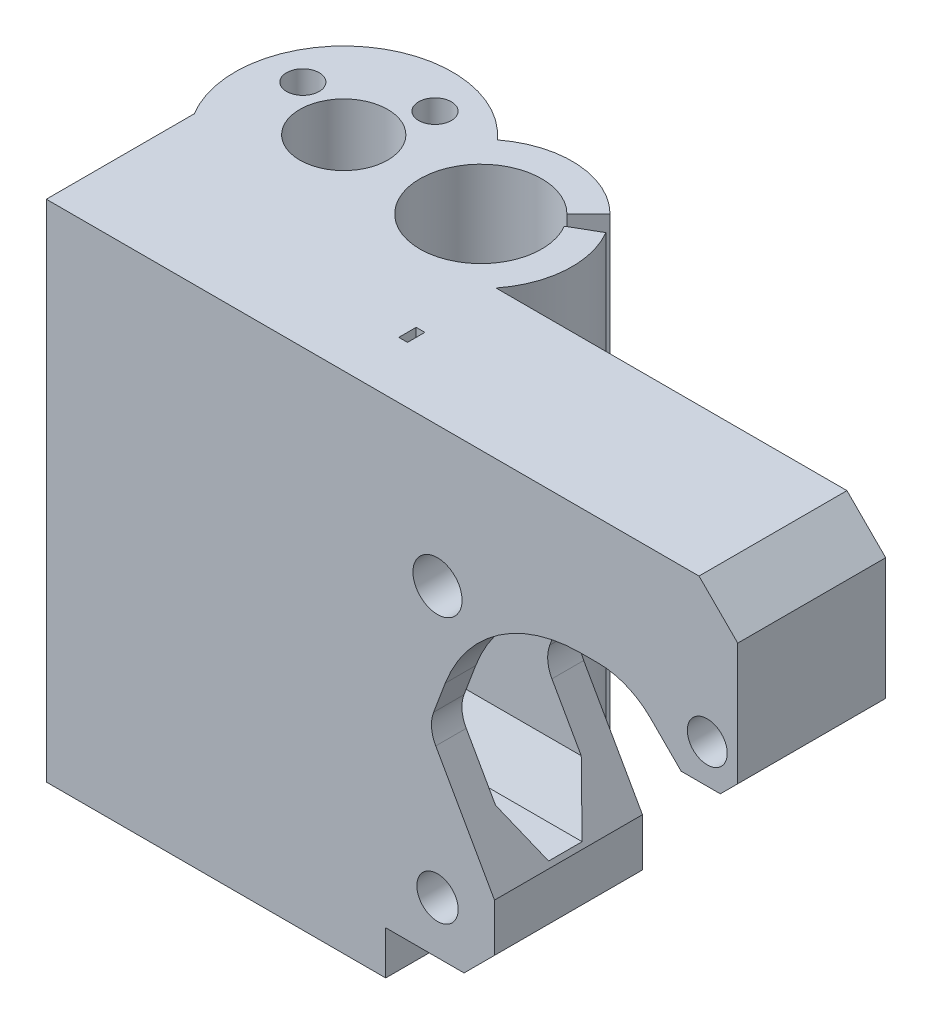
SolidWorks part; units mm, degrees
ref_plane "Front Plane" through (0, 0, 0) normal (0, 0, 1) x (1, 0, 0)
ref_plane "Top Plane" through (0, 0, 0) normal (0, 1, 0) x (1, 0, 0)
ref_plane "Right Plane" through (0, 0, 0) normal (1, 0, 0) x (0, 0, -1)
sketch "Sketch1" plane through (0, 0, 0) normal (0, 0, 1) x (1, 0, 0)
  line L0 (39, -53) -> (48, -53)
  line L1 (0, 0) -> (39, 0)
  line L2 (0, 0) -> (0, -58)
  line L3 (0, -58) -> (39, -58)
  line L4 (39, -53) -> (39, -58)
  line L5 (39, 0) -> (75, 0)
  line L6 (75, 0) -> (79.45, -4.45)
  line L7 (79.45, -4.45) -> (79.45, -18.45)
  line L8 (79.45, -18.45) -> (77.45, -20.45)
  line L9 (77.45, -20.45) -> (72.95, -20.45)
  line L10 (72.95, -20.45) -> (69.45, -16.95)
  line L12 (45.8405, -25.2376) -> (44.5009, -28.8048)
  line L13 (44.75, -32.0294) -> (51.5, -44)
  line L14 (51.5, -44) -> (51.5, -49.5)
  line L15 (61.4145, -14.45) -> (63.4145, -14.45)
  line L16 (51.5, -49.5) -> (48, -53)
  arc A5 (63.4145, -14.45) -> (69.45, -16.95) centre (63.4145, -22.9855) cw
  arc A6 (61.4145, -14.45) -> (45.8405, -25.2376) centre (61.4145, -31.0859) ccw
  arc A7 (44.5009, -28.8048) -> (44.75, -32.0294) centre (48.083, -30.15) ccw
  dimension "D1" = 58
  dimension "D2" = 39
  dimension "D3" = 75
  dimension "D4" = 4.45
  dimension "D5" = 135
  dimension "D6" = 14
  dimension "D7" = 2
  dimension "D8" = 3.5
  dimension "D9" = 6
  dimension "D10" = 5
  dimension "D11" = 4.5
  dimension "D12" = 130
  dimension "D13" = 3.5
  dimension "D14" = 5.5
  dimension "D15" = 6.75
  dimension "D16" = 9
  dimension "D17" = 13.85
  dimension "D18" = 3.417
  dimension "D19" = 2
extrude "Boss-Extrude1" add sketch "Sketch1" along normal blind 17
sketch "Sketch2" plane through (0, 0, 0) normal (0, 1, 0) x (1, 0, 0)
  line L0 (0, -17) -> (0, 6.5) construction
  line L1 (0, 6.5) -> (26.427, 6.5) construction
  circle A0 centre (26.427, 6.5) radius 10.5
  dimension "D2" = 21
  dimension "D1" = 23.5
  dimension "D3" = 26.427
extrude "Boss-Extrude2" add sketch "Sketch2" against normal up to surface (58 mm away) up to face at (19.5, -58, 8.5)
sketch "Sketch3" plane through (0, 0, 0) normal (0, 1, 0) x (1, 0, 0)
  line L0 (0, -17) -> (0, 20.4292) construction
  line L1 (10.6771, 6.5) -> (0, 6.5) construction
  line L2 (75, -17) -> (0, -17) construction
  circle A0 centre (10.6771, 6.5) radius 12.5
  dimension "D3" = 25
  dimension "D2" = 23.5
extrude "Boss-Extrude3" add sketch "Sketch3" against normal blind 13.5
sketch "Sketch4" plane through (0, 0, 0) normal (0, 1, 0) x (1, 0, 0)
  circle A0 centre (26.427, 6.5) radius 7
  circle A1 centre (10.6771, 6.5) radius 5.05
  dimension "D1" = 10.1
  dimension "D2" = 14
extrude "Cut-Extrude1" cut sketch "Sketch4" against normal through all
sketch "Sketch5" plane through (0, 0, 0) normal (-1, 0, 0) x (0, 0, 1)
  line L0 (10.5, -43.5) -> (6.65, -43.5)
  line L1 (6.65, -43.5) -> (3.65, -38)
  line L2 (3.65, -38) -> (3.65, -19)
  line L3 (3.65, -19) -> (6.65, -16)
  line L4 (6.65, -16) -> (10.5, -16)
  line L5 (10.5, -16) -> (13.5, -19)
  line L6 (13.5, -19) -> (13.5, -38)
  line L7 (13.5, -38) -> (10.5, -43.5)
  line L8 (17, 0) -> (0, 0) construction
  line L9 (17, 0) -> (17, -58) construction
  circle A0 centre (8.5, -6) radius 4.05
  circle A1 centre (8.5, -51) radius 4.05
  dimension "D8" = 8.1
  dimension "D9" = 8.1
  dimension "D1" = 19
  dimension "D2" = 3
  dimension "D3" = 3.85
  dimension "D4" = 16
  dimension "D5" = 6
  dimension "D6" = 51
  dimension "D7" = 5.5
  dimension "D10" = 3
  dimension "D11" = 3
  dimension "D12" = 19
  dimension "D13" = 3.85
  dimension "D14" = 3
  dimension "D15" = 3
  dimension "D16" = 3.5
  dimension "D17" = 8.5
  dimension "D18" = 8.5
extrude "Cut-Extrude2" cut sketch "Sketch5" against normal blind 35
sketch "Sketch6" plane through (0, 0, 0) normal (0, 0, -1) x (-1, 0, 0)
  line L0 (-75.9503, -16.0252) -> (-44.9503, -16.0252) construction
  line L1 (-44.9503, -16.0252) -> (-44.9503, -47.0252) construction
  line L2 (-44.9503, -47.0252) -> (-75.9503, -47.0252) construction
  line L3 (-75.9503, -47.0252) -> (-75.9503, -16.0252) construction
  line L4 (-75.9503, -31.5252) -> (-44.9503, -31.5252) construction
  line L5 (-60.4503, -16.0252) -> (-60.4503, -47.0252) construction
  circle A0 centre (-75.9503, -16.0252) radius 2.2933
  circle A1 centre (-44.9503, -16.0252) radius 2.8225
  circle A2 centre (-44.9503, -47.0252) radius 2.3733
  circle A3 centre (-60.4503, -31.5252) radius 11 construction
  point P14 (-60.4503, -31.5252)
  dimension "D3" = 22
  dimension "D1" = 31
  dimension "D2" = 31
extrude "Cut-Extrude3" cut sketch "Sketch6" against normal through all
sketch "Sketch8" plane through (35, 0, 0) normal (-1, 0, 0) x (0, 0, 1)
  line L8 (10.5, -43.5) -> (13.5, -38)
  line L9 (13.5, -38) -> (13.5, -19)
  line L10 (13.5, -19) -> (10.5, -16)
  line L11 (10.5, -16) -> (6.65, -16)
  line L12 (6.65, -16) -> (3.65, -19)
  line L13 (3.65, -19) -> (3.65, -38)
  line L14 (3.65, -38) -> (6.65, -43.5)
  line L15 (6.65, -43.5) -> (10.5, -43.5)
  line L16 (10.5, -43.5) -> (13.5, -38)
  line L17 (13.5, -38) -> (13.5, -19)
  line L18 (13.5, -19) -> (10.5, -16)
  line L19 (10.5, -16) -> (6.65, -16)
  line L20 (6.65, -16) -> (3.65, -19)
  line L21 (3.65, -19) -> (3.65, -38)
  line L22 (3.65, -38) -> (6.65, -43.5)
  line L23 (6.65, -43.5) -> (10.5, -43.5)
  dimension "D1" = 0
extrude "Cut-Extrude4" cut sketch "Sketch8" against normal blind 20
sketch "Sketch9" plane through (0, 0, 0) normal (0, 1, 0) x (1, 0, 0)
  line L0 (32.4461, 10.0735) -> (35.4774, 11.8236)
  line L1 (31.3767, 11.4497) -> (33.8516, 13.9246)
  line L2 (26.427, 6.5) -> (36.927, 6.5) construction
  line L3 (32.4461, 10.0735) -> (26.427, 6.5) construction
  line L4 (26.427, 6.5) -> (31.3767, 11.4497) construction
  arc A0 (32.4461, 10.0735) -> (31.3767, 11.4497) centre (26.427, 6.5) ccw
  arc A1 (35.4774, 11.8236) -> (33.8516, 13.9246) centre (26.427, 6.5) ccw
  arc A2 (34.6732, 0) -> (20.0124, 14.8128) centre (26.427, 6.5) ccw construction
  circle A3 centre (26.427, 6.5) radius 7 construction
  dimension "D1" = 15
  dimension "D2" = 30
extrude "Cut-Extrude5" cut sketch "Sketch9" against normal through all
sketch "Sketch10" plane through (0, 0, 0) normal (0, 1, 0) x (1, 0, 0)
  line L0 (13.5702, 14.0925) -> (10.6771, 6.5) construction
  line L1 (10.6771, 6.5) -> (3.0846, 9.3931) construction
  circle A0 centre (13.5702, 14.0925) radius 1.875
  circle A1 centre (3.0846, 9.3931) radius 1.875
  dimension "D3" = 3.75
  dimension "D4" = 3.75
  dimension "D1" = 90
  dimension "D2" = 8.125
  dimension "D5" = 8.125
extrude "Cut-Extrude6" cut sketch "Sketch10" against normal through all
sketch "Sketch11" plane through (0, -58, 0) normal (0, -1, 0) x (1, 0, 0)
  line L0 (0, 17) -> (0, 0) construction
  line L1 (35, 8.5) -> (34, 8.5)
  line L2 (35, 8.5) -> (35, 10.5)
  line L3 (35, 10.5) -> (34, 10.5)
  line L4 (34, 8.5) -> (34, 10.5)
  line L5 (0, 17) -> (39, 17) construction
  dimension "D1" = 35
  dimension "D2" = 1
  dimension "D3" = 2
  dimension "D4" = 6.5
extrude "Cut-Extrude7" cut sketch "Sketch11" against normal blind 8
ref_plane "Plane1" through (0, -29, 0) normal (0, 1, 0) x (1, 0, 0)
mirror "Mirror1" about plane through (0, -29, 0) normal (0, 1, 0) of "Cut-Extrude7"
